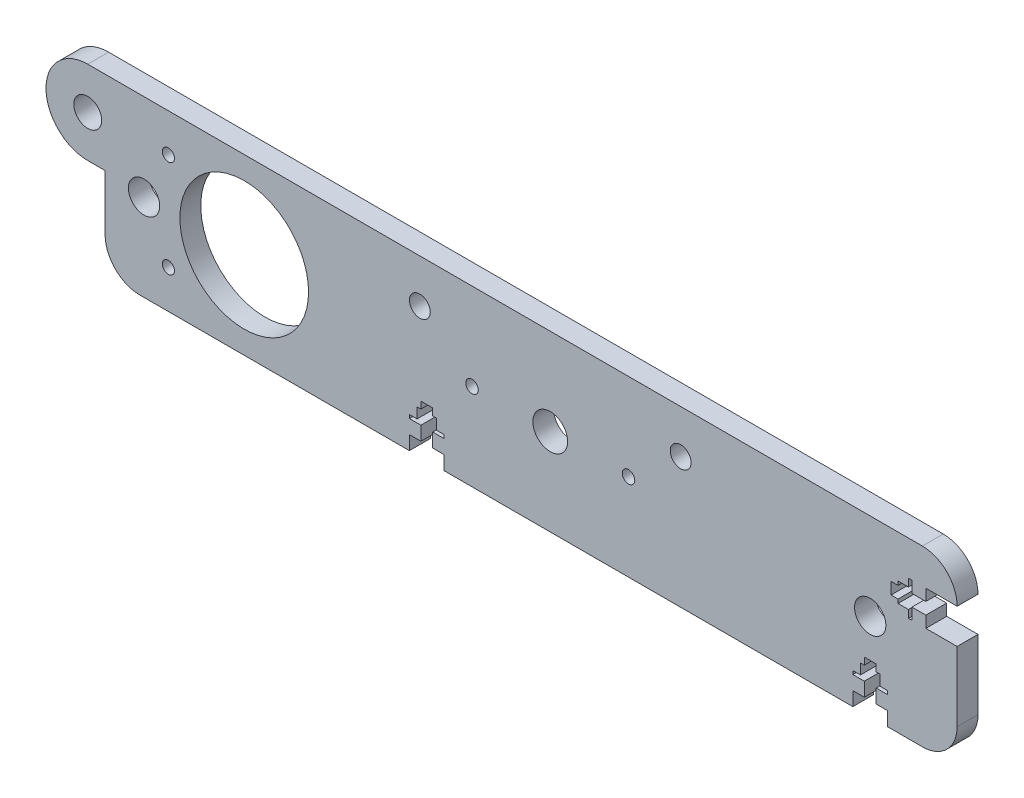
SolidWorks part; units mm, degrees
material "Balsa"
ref_plane "Plano frontal" through (0, 0, 0) normal (0, 0, 1) x (1, 0, 0)
ref_plane "Plano superior" through (0, 0, 0) normal (0, 1, 0) x (1, 0, 0)
ref_plane "Plano direito" through (0, 0, 0) normal (1, 0, 0) x (0, 0, -1)
sketch "Esboço1" plane through (0, 0, 0) normal (0, 0, 1) x (1, 0, 0)
  line L0 (105, -25) -> (105, -21)
  line L1 (-110, -25) -> (-32.5, -25)
  line L2 (-125, 1) -> (-120, 1)
  line L3 (-125, 25) -> (115, 25)
  line L4 (125, 5) -> (125, -15)
  line L6 (-120, 1) -> (-120, -15)
  line L7 (-80, 18.5) -> (-80, 25) construction
  line L8 (8, 25) -> (8, 0) construction
  line L9 (-104.31, 0) -> (-104.31, 1.5)
  line L10 (-29.5, 12.5) -> (45.5, 12.5) construction
  line L11 (-14.5, 0) -> (30.5, 0) construction
  line L12 (105, -21) -> (101.7, -21)
  line L13 (95, -21) -> (95, -25)
  line L14 (-32.5, -25) -> (-32.5, -21)
  line L15 (-32.5, -21) -> (-29.2, -21)
  line L16 (-22.5, -21) -> (-22.5, -25)
  line L17 (-22.5, -25) -> (95, -25)
  line L18 (-27.5, -25) -> (-27.5, -13.0244) construction
  line L19 (-29.2, -21) -> (-29.2, -17)
  line L20 (-29.2, -17) -> (-32.5, -17)
  line L21 (-30.3, -16) -> (-30.3, -13)
  line L22 (-30.3, -13) -> (-29.2, -13)
  line L23 (-32.5, -25) -> (-22.5, -25) construction
  line L24 (-29.2, -13) -> (-29.2, -11)
  line L25 (-29.2, -11) -> (-25.8, -11)
  line L26 (-30.3, -16) -> (-32.5, -16)
  line L27 (-32.5, -16) -> (-32.5, -17)
  line L28 (-22.5, -16) -> (-22.5, -17)
  line L29 (-24.7, -16) -> (-22.5, -16)
  line L30 (-25.8, -13) -> (-25.8, -11)
  line L31 (-24.7, -13) -> (-25.8, -13)
  line L32 (-24.7, -16) -> (-24.7, -13)
  line L33 (-25.8, -17) -> (-22.5, -17)
  line L34 (-25.8, -21) -> (-25.8, -17)
  line L35 (-22.5, -21) -> (-25.8, -21)
  line L36 (105, -16) -> (105, -17)
  line L37 (95, -16) -> (95, -17)
  line L38 (101.7, -17) -> (105, -17)
  line L39 (98.3, -17) -> (95, -17)
  line L40 (101.7, -13) -> (101.7, -11)
  line L41 (102.8, -13) -> (101.7, -13)
  line L42 (98.3, -13) -> (98.3, -11)
  line L43 (98.3, -11) -> (101.7, -11)
  line L44 (98.3, -21) -> (98.3, -17)
  line L45 (100, -25) -> (100, -21) construction
  line L46 (97.2, -16) -> (97.2, -13)
  line L47 (101.7, -21) -> (101.7, -17)
  line L48 (102.8, -16) -> (105, -16)
  line L49 (97.2, -16) -> (95, -16)
  line L50 (97.2, -13) -> (98.3, -13)
  line L51 (102.8, -16) -> (102.8, -13)
  line L52 (98.3, -21) -> (95, -21)
  line L53 (95, -25) -> (105, -25) construction
  line L54 (115, -25) -> (105, -25)
  line L55 (125, 15) -> (116, 15)
  line L56 (116, 15) -> (116, 11.7)
  line L57 (116, 5) -> (125, 5)
  line L58 (111, 15) -> (112, 15)
  line L59 (111, 5) -> (112, 5)
  line L60 (112, 11.7) -> (112, 15)
  line L61 (112, 8.3) -> (112, 5)
  line L62 (108, 11.7) -> (106, 11.7)
  line L63 (108, 12.8) -> (108, 11.7)
  line L64 (108, 8.3) -> (106, 8.3)
  line L65 (106, 8.3) -> (106, 11.7)
  line L66 (116, 8.3) -> (112, 8.3)
  line L67 (111, 7.2) -> (108, 7.2)
  line L68 (116, 11.7) -> (112, 11.7)
  line L69 (111, 12.8) -> (111, 15)
  line L70 (111, 7.2) -> (111, 5)
  line L71 (108, 7.2) -> (108, 8.3)
  line L72 (111, 12.8) -> (108, 12.8)
  line L73 (116, 8.3) -> (116, 5)
  line L74 (-108.81, 0) -> (-76.55, 0) construction
  circle A0 centre (-80, 0) radius 18.5
  circle A1 centre (100, 0) radius 4.5
  arc A2 (125, -15) -> (115, -25) centre (115, -15) cw
  arc A3 (115, 25) -> (125, 15) centre (115, 15) cw
  arc A4 (-125, 25) -> (-125, 1) centre (-125, 13) ccw
  arc A5 (-120, -15) -> (-110, -25) centre (-110, -15) ccw
  circle A6 centre (8, 0) radius 5
  circle A7 centre (-108.81, 0) radius 4.5
  circle A8 centre (-14.5, 0) radius 1.8
  circle A9 centre (30.5, 0) radius 1.8
  circle A10 centre (-29.5, 12.5) radius 3
  circle A11 centre (45.5, 12.5) radius 3
  circle A12 centre (-101.81, 14) radius 1.75
  circle A13 centre (-101.81, -14) radius 1.75
  circle A14 centre (-125, 13) radius 4
  point P0 (0, 0)
  point P34 (8, 12.5)
  point P35 (8, 0)
  point P42 (8, 12.5)
  point P60 (-27.5, -25)
  point P67 (-27.5, -11)
  point P84 (94.8463, -8.5)
  point P89 (100, -25)
  point P108 (103.5, 9.8463)
  dimension "D3" = 37
  dimension "D5" = 9
  dimension "D6" = 10
  dimension "D9" = 28.81
  dimension "D10" = 75
  dimension "D11" = 6
  dimension "D12" = 3.6
  dimension "D14" = 10
  dimension "D40" = 3.5
  dimension "D42" = 12
  dimension "D43" = 8
  dimension "D45" = 10
  dimension "D4" = 180
  dimension "D7" = 4
  dimension "D8" = 10
  dimension "D13" = 45
  dimension "D15" = 4
  dimension "D16" = 10
  dimension "D17" = 4
  dimension "D18" = 4
  dimension "D19" = 4
  dimension "D20" = 5.6
  dimension "D21" = 3.4
  dimension "D22" = 2
  dimension "D23" = 1
  dimension "D24" = 10
  dimension "D25" = 4
  dimension "D26" = 5.6
  dimension "D27" = 25
  dimension "D28" = 2
  dimension "D29" = 4
  dimension "D30" = 1
  dimension "D31" = 10
  dimension "D32" = 2
  dimension "D33" = 8
  dimension "D34" = 4
  dimension "D35" = 127.5
  dimension "D36" = 3.4
  dimension "D37" = 25
  dimension "D38" = 7
  dimension "D39" = 14
  dimension "D41" = 50
  dimension "D44" = 5
extrude "Ressalto-extrusão1" add sketch "Esboço1" along normal blind 6 contours L1 A3 L3 A11 A10 A9 A8 A6 A1 A0 A7 region at (107.6673, -23, 0)
